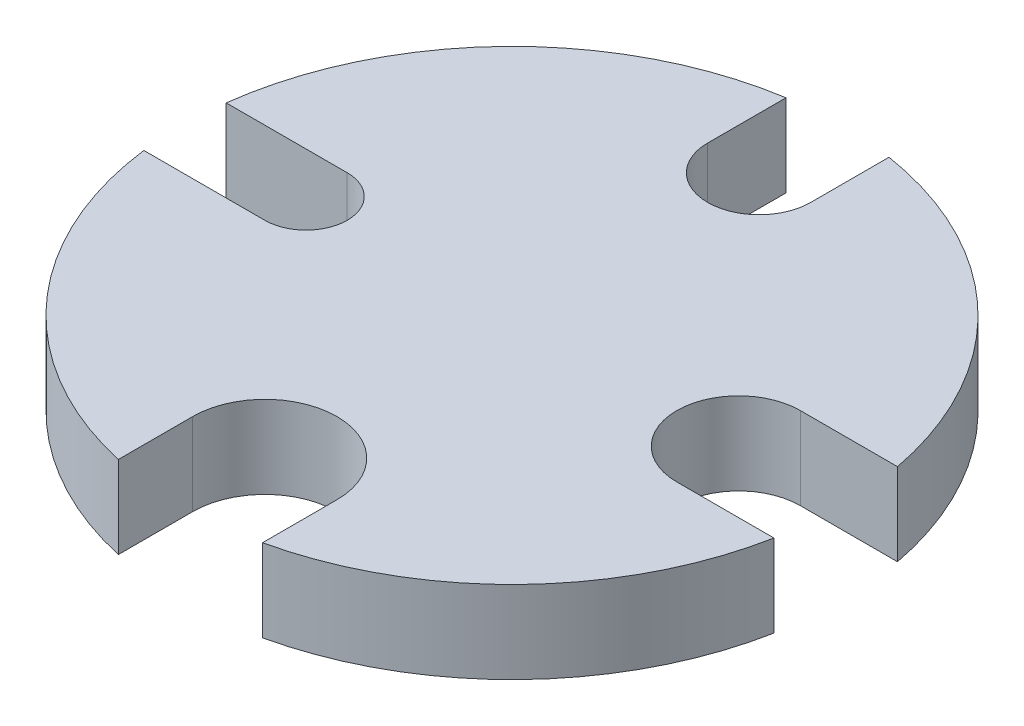
SolidWorks part; units mm, degrees
note: '?' marks a value the reader was unsure of.
ref_plane "Front Plane" through (0, 0, 0) normal (0, 0, 1) x (1, 0, 0)
ref_plane "Top Plane" through (0, 0, 0) normal (0, 1, 0) x (1, 0, 0)
ref_plane "Right Plane" through (0, 0, 0) normal (1, 0, 0) x (0, 0, -1)
sketch "Sketch1" plane through (0, 0, 0) normal (0, 1, 0) x (1, 0, 0)
  line L0 (-22.225, -99.1393) -> (-22.225, -76.2)
  line L1 (22.225, -76.2) -> (22.225, -99.1393)
  line L2 (-15.875, 100.3521) -> (-15.875, 76.2)
  line L3 (15.875, 100.3521) -> (15.875, 76.2)
  line L4 (99.7981, 19.05) -> (69.85, 19.05)
  line L5 (99.7981, -19.05) -> (69.85, -19.05)
  line L6 (-100.8031, 12.7) -> (-63.5, 12.7)
  line L7 (-100.8031, -12.7) -> (-63.5, -12.7)
  circle A0 centre (0, 0) radius 101.6
  arc A1 (-22.225, -76.2) -> (22.225, -76.2) centre (0, -76.2) cw
  arc A2 (-15.875, 76.2) -> (15.875, 76.2) centre (0, 76.2) ccw
  arc A3 (69.85, 19.05) -> (69.85, -19.05) centre (69.85, 0) ccw
  arc A4 (-63.5, 12.7) -> (-63.5, -12.7) centre (-63.5, 0) cw
  spline S0 degree 2 poles (-100.8031, 12.7) (-102.3969, 0) (-100.8031, -12.7) knots 0 0 0 1 1 1
  spline S1 degree 2 poles (-15.875, 100.3521) (0, 102.8479) (15.875, 100.3521) knots 0 0 0 1 1 1
  spline S2 degree 2 poles (99.7981, 19.05) (103.4019, 0) (99.7981, -19.05) knots 0 0 0 1 1 1
  spline S3 degree 2 poles (-22.225, -99.1393) (0, -104.0607) (22.225, -99.1393) knots 0 0 0 1 1 1
  point P26 (22.225, -87.6697)
  point P27 (50.8, 0)
  dimension "D1" = 203.2
  dimension "D3" = 76.2
  dimension "D9" = 63.5
  dimension "D2" = 44.45
  dimension "D4" = 38.1
  dimension "D5" = 50.8
  dimension "D6" = 31.75
  dimension "D7" = 76.2
  dimension "D8" = 25.4
extrude "Boss-Extrude1" add sketch "Sketch1" along normal blind 25.4 contours L6 A4 L7 A0 L0 A1 L1 L5 A3 L4 L3 A2 L2
sketch "Sketch2" plane through (0, 0, 0) normal (1, 0, 0) x (0, 0, -1)
  line L0 (0, 0) -> (0, 26.4564) construction
ref_axis "Axis1" through (0, 0, 0) along (0, 1, 0)?
